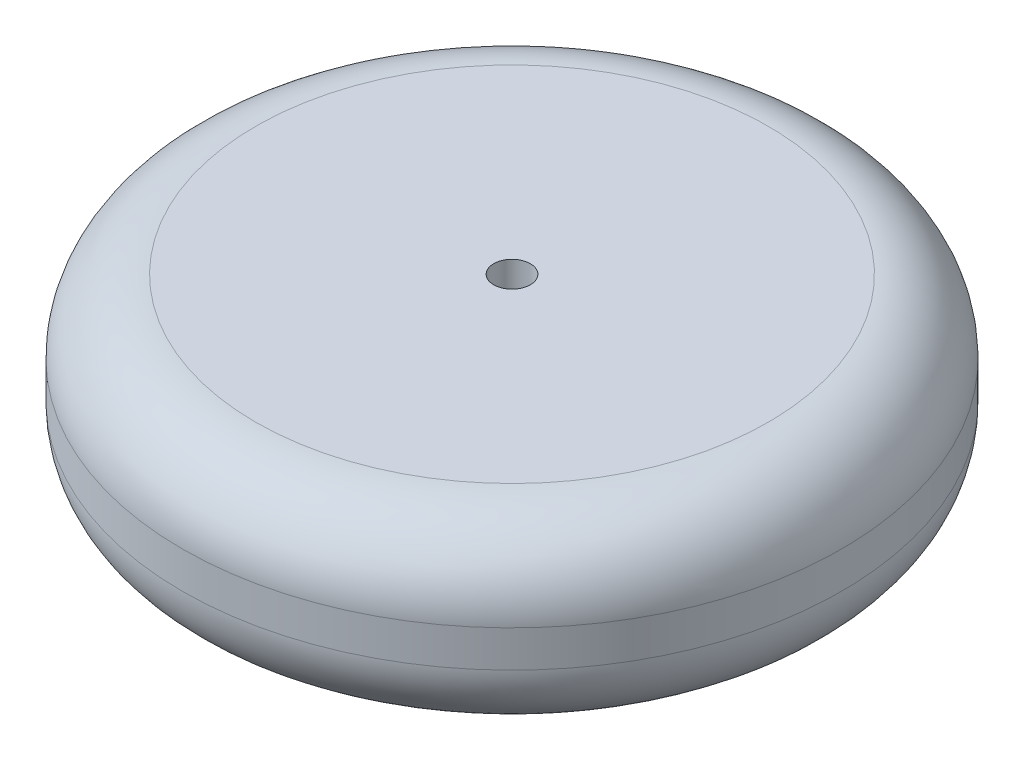
SolidWorks part; units mm, degrees
ref_plane "Front Plane" through (0, 0, 0) normal (0, 0, 1) x (1, 0, 0)
ref_plane "Top Plane" through (0, 0, 0) normal (0, 1, 0) x (1, 0, 0)
ref_plane "Right Plane" through (0, 0, 0) normal (1, 0, 0) x (0, 0, -1)
sketch "Sketch1" plane through (0, 0, 0) normal (0, 1, 0) x (1, 0, 0)
  circle A0 centre (0, 0) radius 114.3
extrude "Boss-Extrude1" add sketch "Sketch1" along normal blind 31.75 and the other way blind 31.75
fillet "Fillet1" radius 25.4 2 edges at (0, -31.75, 114.3) (0, 31.75, 114.3)
sketch "Sketch2" plane through (0, 31.75, 0) normal (0, 1, 0) x (1, 0, 0)
  circle A0 centre (0, 0) radius 6.35
extrude "Cut-Extrude1" cut sketch "Sketch2" against normal blind 107.188
